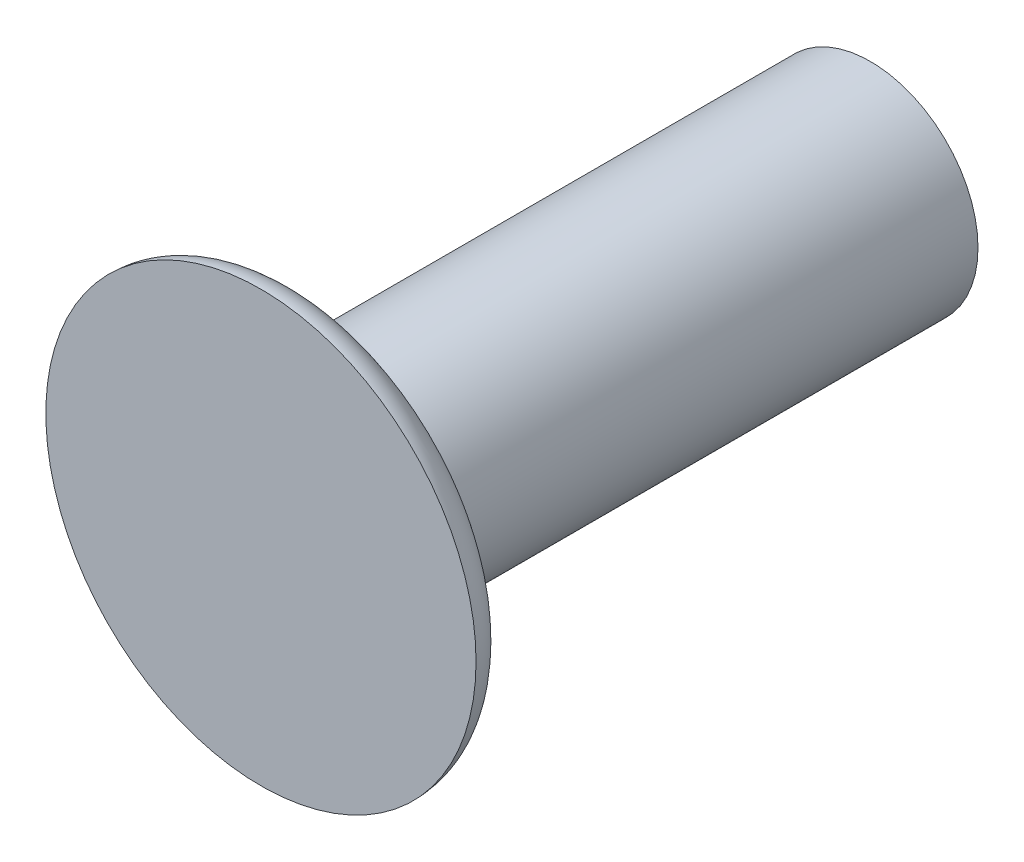
SolidWorks part; units mm, degrees
ref_plane "Front Plane" through (0, 0, 0) normal (0, 0, 1) x (1, 0, 0)
ref_plane "Top Plane" through (0, 0, 0) normal (0, 1, 0) x (1, 0, 0)
ref_plane "Right Plane" through (0, 0, 0) normal (1, 0, 0) x (0, 0, -1)
sketch "Sketch1" plane through (0, 0, 0) normal (0, 0, 1) x (1, 0, 0)
  circle A0 centre (0, 0) radius 15
  dimension "D1" = 30
extrude "Boss-Extrude1" add sketch "Sketch1" along normal blind 80
sketch "Sketch2" plane through (0, 0, 80) normal (0, 0, 1) x (1, 0, 0)
  circle A0 centre (0, 0) radius 30
  dimension "D1" = 60
extrude "Boss-Extrude2" add sketch "Sketch2" along normal blind 5
fillet "Fillet1" radius 5 2 edges at (30, 0, 80) (15, 0, 80)
sketch "Sketch3" plane through (0, 0, 0) normal (0, 0, -1) x (-1, 0, 0)
  line L0 (0, -5) -> (0, 5) construction
  circle A0 centre (0, 5) radius 2
  circle A1 centre (0, -5) radius 2
  point P5 (0, 0)
  dimension "D2" = 4
  dimension "D1" = 10
extrude "Cut-Extrude1" cut sketch "Sketch3" against normal blind 5
